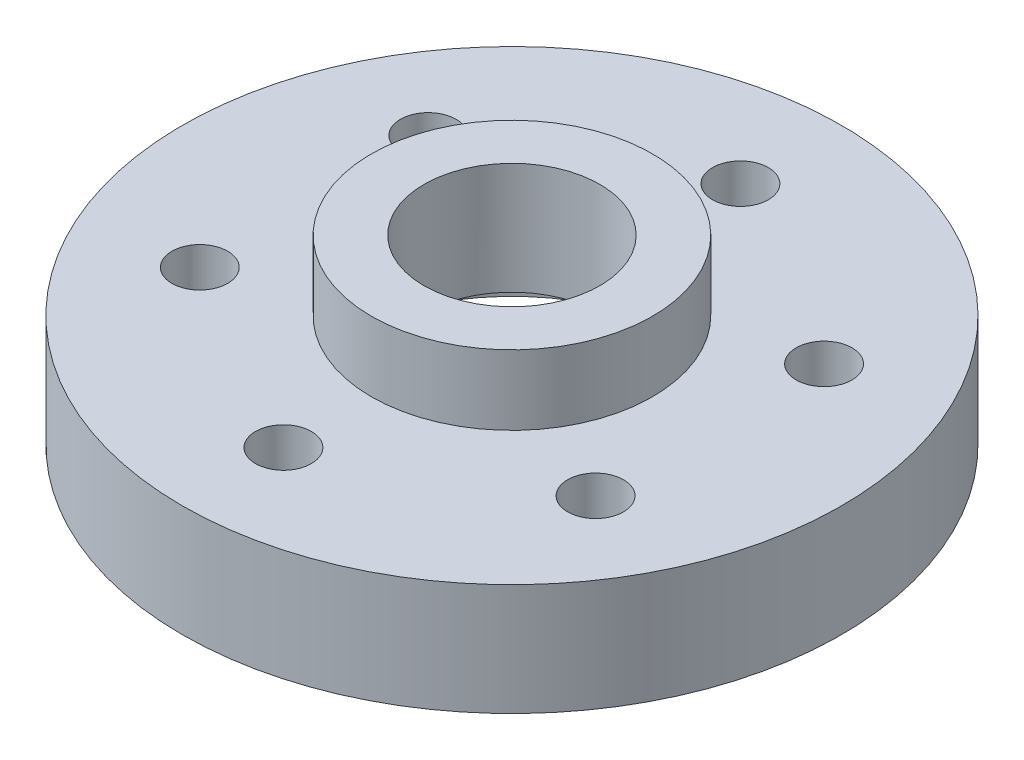
SolidWorks part; units mm, degrees
material "6061-T6 (SS)"
ref_plane "Front Plane" through (0, 0, 0) normal (0, 0, 1) x (1, 0, 0)
ref_plane "Top Plane" through (0, 0, 0) normal (0, 1, 0) x (1, 0, 0)
ref_plane "Right Plane" through (0, 0, 0) normal (1, 0, 0) x (0, 0, -1)
sketch "Sketch1" plane through (0, 0, 0) normal (0, 1, 0) x (1, 0, 0)
  circle A0 centre (0, 0) radius 37.5
  circle A1 centre (0, 0) radius 10
  dimension "D1" = 75
  dimension "D2" = 20
extrude "Boss-Extrude1" add sketch "Sketch1" against normal blind 12.7
sketch "Sketch2" plane through (0, 0, 0) normal (0, 1, 0) x (1, 0, 0)
  circle A0 centre (0, 0) radius 16
  circle A1 centre (0, 0) radius 10 construction
  circle A2 centre (0, 0) radius 10
  dimension "D1" = 32
extrude "Boss-Extrude2" add sketch "Sketch2" along normal blind 7.9375
sketch "Sketch3" plane through (0, -12.7, 0) normal (0, -1, 0) x (1, 0, 0)
  circle A0 centre (0, 0) radius 20.6375
  dimension "D1" = 41.275
extrude "Cut-Extrude1" cut sketch "Sketch3" against normal blind 7.9375
sketch "Sketch4" plane through (0, -12.7, 0) normal (0, -1, 0) x (1, 0, 0)
  circle A0 centre (0, 26) radius 3.175
  dimension "D2" = 6.35
  dimension "D1" = 26
extrude "Cut-Extrude2" cut sketch "Sketch4" against normal through all
pattern_circular "CirPattern1" count 6 over 360 about axis through (0, -12.7, 0) along (0, -1, 0) of "Cut-Extrude2"
equation "\"D1@Boss-Extrude2\"=0.375in-0.0625in"
equation "\"D2@Sketch4\"=0.25in"
